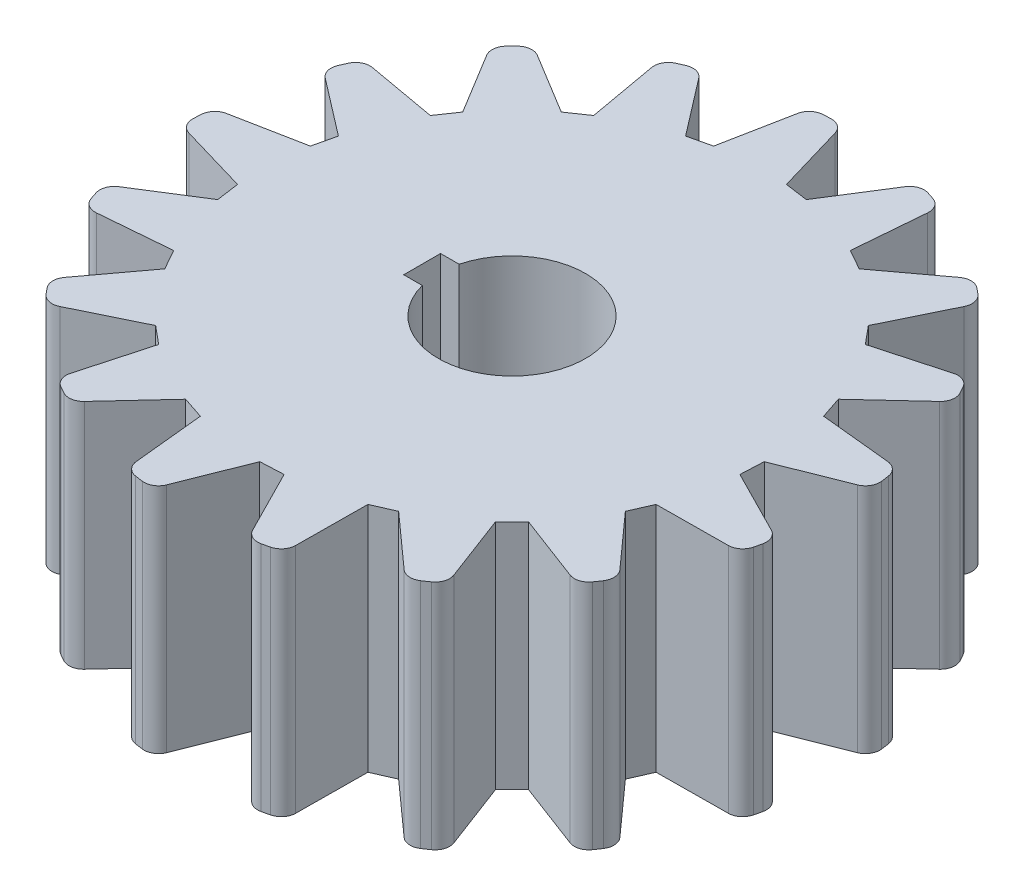
SolidWorks part; units mm, degrees
note: '?' marks a value the reader was unsure of.
ref_plane "Plan de face" through (0, 0, 0) normal (0, 0, 1) x (1, 0, 0)
ref_plane "Plan de dessus" through (0, 0, 0) normal (0, 1, 0) x (1, 0, 0)
ref_plane "Plan de droite" through (0, 0, 0) normal (1, 0, 0) x (0, 0, -1)
sketch "Esquisse1" plane through (0, 0, 0) normal (0, 0, 1) x (1, 0, 0)
  line L0 (-57, 40) -> (-57, 0)
  line L1 (-50, 40) -> (0, 40)
  line L2 (0, 40) -> (0, 0)
  line L3 (0, 40) -> (0, 0) construction
  line L4 (0, 0) -> (-50, 0)
  line L18 (-57, 40) -> (-50, 40)
  line L19 (-50, 40) -> (-50, 0) construction
  line L20 (-50, 0) -> (-57, 0)
  dimension "D2" = 40
  dimension "D3" = 57
  dimension "D15" = 50
revolve "Révolution1" add sketch "Esquisse1" angle 360 about L3
sketch "Esquisse5" plane through (0, 40, 0) normal (0, 1, 0) x (1, 0, 0)
  line L0 (0, 0) -> (0, 57) construction
  line L1 (0, 0) -> (-20.5908, 53.1509) construction
  line L2 (-20.5908, 53.1509) -> (-11.9043, 41.8394)
  line L3 (-11.9043, 41.8394) -> (-7.9931, 42.7593)
  line L4 (-7.9931, 42.7593) -> (-5.2593, 56.7568)
  line L5 (-5.2593, 56.7568) -> (0, 57)
  line L6 (-5.2593, 56.7568) -> (0, 0) construction
  line L7 (-7.9931, 42.7593) -> (0, 0) construction
  line L8 (-11.9043, 41.8394) -> (0, 0) construction
  line L9 (0, 57) -> (0, 108.0563)
  line L10 (0, 108.0563) -> (-38.2804, 98.3017)
  line L11 (-38.2804, 98.3017) -> (-20.5908, 53.1509)
  circle A0 centre (0, 0) radius 57 construction
  circle A1 centre (0, 0) radius 43.5 construction
  circle A2 centre (0, 0) radius 57 construction
  dimension "D1" = 21.176
  dimension "D2" = 5.294
  dimension "D3" = 5.294
  dimension "D5" = 87
  dimension "D4" = 5.294
extrude "Enlèv. mat.-Extru.3" cut sketch "Esquisse5" against normal through all
fillet "Congé1" radius 2.5 2 edges at (-20.5908, 20, -53.1509) (-5.2593, 20, -56.7568)
ref_axis "Axe1" through (0, 39.3, 0) along (0, -1, 0)?
pattern_circular "Répétition circulaire1" count 17 over 360 about axis through (0, 0, 0) along (0, 1, 0) of "Enlèv. mat.-Extru.3", "Congé1"
sketch "Esquisse6" plane through (0, 40, 0) normal (0, 1, 0) x (1, 0, 0)
  line L0 (0, 0) -> (-12.7, 0) construction
  line L1 (-12.2967, 3.175) -> (-15.4967, 3.175)
  line L2 (-15.4967, 3.175) -> (-15.4967, -3.175)
  line L3 (-15.4967, -3.175) -> (-12.2967, -3.175)
  line L4 (-12.7, 0) -> (-15.4967, 0) construction
  circle A0 centre (0, 0) radius 12.7 construction
  arc A1 (-12.2967, 3.175) -> (-12.2967, -3.175) centre (0, 0) cw
  dimension "D3" = 25.4
  dimension "D1" = 6.35
  dimension "D2" = 3.2
extrude "Enlèv. mat.-Extru.4" cut sketch "Esquisse6" against normal through all
